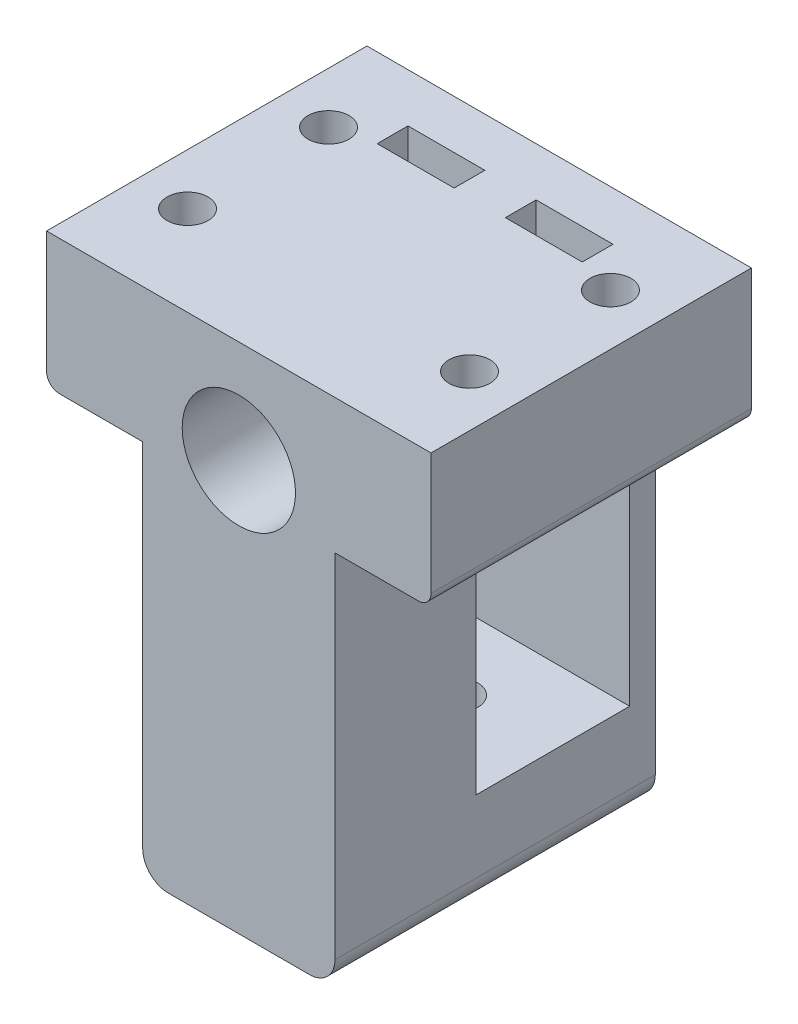
SolidWorks part; units mm, degrees
material "Polyetheretherketone (PEEK)"
ref_plane "Front Plane" through (0, 0, 0) normal (0, 0, 1) x (1, 0, 0)
ref_plane "Top Plane" through (0, 0, 0) normal (0, 1, 0) x (1, 0, 0)
ref_plane "Right Plane" through (0, 0, 0) normal (1, 0, 0) x (0, 0, -1)
sketch "Sketch1" plane through (0, 0, 0) normal (0, 0, 1) x (1, 0, 0)
  line L0 (0, 40) -> (0, 50.5)
  line L3 (0, 50.5) -> (30, 50.5)
  line L7 (0, 40) -> (7.5, 40)
  line L8 (7.5, 10.5) -> (7.5, 40)
  line L11 (30, 40) -> (22.5, 40)
  line L12 (22.5, 10.5) -> (22.5, 40)
  line L13 (30, 40) -> (30, 50.5)
  line L14 (7.5, 10.5) -> (22.5, 10.5)
extrude "Boss-Extrude1" add sketch "Sketch1" along normal blind 25
sketch "Sketch2" plane through (7.5, 0, 0) normal (-1, 0, 0) x (0, 0, 1)
  line L1 (2, 18.13) -> (14, 18.13)
  line L2 (2, 18.13) -> (2, 34.13)
  line L3 (2, 34.13) -> (14, 34.13)
  line L4 (14, 18.13) -> (14, 34.13)
extrude "Cut-Extrude1" cut sketch "Sketch2" against normal through all
sketch "Sketch3" plane through (0, 50.5, 0) normal (0, 1, 0) x (1, 0, 0)
  circle A0 centre (4, -7) radius 1.6
  circle A1 centre (26, -7) radius 1.6
  circle A2 centre (26, -18) radius 1.6
  circle A3 centre (4, -18) radius 1.6
extrude "Cut-Extrude2" cut sketch "Sketch3" against normal through all
sketch "Sketch4" plane through (0, 10.5, 0) normal (0, -1, 0) x (1, 0, 0)
  circle A0 centre (15, 8) radius 1.65
extrude "Cut-Extrude3" cut sketch "Sketch4" against normal up to surface (7.63 mm away) up to face at (15, 18.13, 8)
ref_plane "Plane1" through (0, 0, 15) normal (0, 0, 1) x (1, 0, 0)
sketch "Sketch6" plane through (0, 0, 15) normal (0, 0, 1) x (1, 0, 0)
  circle A0 centre (15, 42.5) radius 4.4196
extrude "Cut-Extrude4" cut sketch "Sketch6" along normal up to surface (10 mm away) up to face at (15, 35.25, 25)
sketch "Sketch7" plane through (0, 0, 0) normal (0, 0, -1) x (-1, 0, 0)
  circle A0 centre (-10, 42.5) radius 1.6
  circle A1 centre (-20, 42.5) radius 1.6
sketch "Sketch8" plane through (0, 0, 0) normal (0, 0, -1) x (-1, 0, 0)
  line L0 (-18.3, 42.5) -> (-11.7, 42.5) construction
  line L1 (-18.3, 45.05) -> (-11.7, 45.05) construction
  line L2 (-18.3, 39.95) -> (-11.7, 39.95) construction
  arc A1 (-18.3, 45.05) -> (-18.3, 39.95) centre (-18.3, 42.5) ccw construction
  arc A2 (-11.7, 39.95) -> (-11.7, 45.05) centre (-11.7, 42.5) ccw construction
  circle A3 centre (-15, 42.5) radius 2.65
  point P3 (-15, 42.5)
extrude "Cut-Extrude6" cut sketch "Sketch8" against normal blind 3
sketch "Sketch9" plane through (0, 34.13, 0) normal (0, -1, 0) x (1, 0, 0)
  circle A0 centre (15, 8) radius 2.45
ref_axis "Axis1" through (15, 34.13, 8) along (0, -1, 0)
ref_plane "Plane2" through (15, 0, 0) normal (-1, 0, 0) x (0, 0, 1)
sketch "Sketch11" plane through (15, 0, 0) normal (-1, 0, 0) x (0, 0, 1)
  line L0 (10.45, 34.13) -> (8, 34.13)
  line L1 (14, 34.13) -> (2, 34.13) construction
  line L2 (5.55, 34.13) -> (10.45, 34.13) construction
  line L3 (8, 34.13) -> (8, 37.36)
  line L4 (8, 37.36) -> (11.15, 37.36)
  line L5 (11.15, 37.36) -> (11.15, 35.66)
  line L6 (10.45, 34.13) -> (10.45, 35.66)
  line L7 (10.45, 35.66) -> (11.15, 35.66)
revolve "Cut-Revolve1" cut sketch "Sketch11" angle 360 about axis through (15, 34.13, 8) along (0, -1, 0) other way angle 360
sketch "Sketch15" plane through (0, 0, 3) normal (0, 0, -1) x (-1, 0, 0)
  circle A1 centre (-15, 42.5) radius 1
ref_plane "Plane3" through (0, 42.5, 0) normal (0, -1, 0) x (-1, 0, 0)
sketch "Sketch16" plane through (0, 42.5, 0) normal (0, -1, 0) x (-1, 0, 0)
  line L0 (-16, -3) -> (-16, -11.0289)
  line L2 (-16.5719, -12.7908) -> (-18.175, -15)
  line L5 (-18.175, -15) -> (-15, -15)
  line L7 (-15, -15) -> (-15, -3)
  line L8 (-15, -3) -> (-16, -3)
  arc A0 (-16.5719, -12.7908) -> (-16, -11.0289) centre (-19, -11.0289) ccw
  dimension "D1" = 3
sketch "Sketch17" plane through (0, 42.5, 0) normal (0, -1, 0) x (-1, 0, 0)
  circle A0 centre (-15, -8) radius 1
loft "Cut-Loft5" cut profiles "Sketch9", "Sketch17" connector at (17.4494, 34.13, 8.0539) connector at (15.9999, 42.5, 8.0126)
ref_axis "Axis2" through (15, 42.5, 25) along (0, 0, -1)
revolve "Cut-Revolve2" cut sketch "Sketch16" angle 360 about axis through (15, 42.5, 25) along (0, 0, -1) other way angle 360
fillet "Fillet4" radius 1 1 edges at (30, 40, 12.5) type face fillet first side face at (30, 45.25, 12.5) second side face at (24.4, 40, 18)
fillet "Fillet5" radius 1 1 edges at (0, 40, 12.5) type face fillet first side face at (0, 45.25, 12.5) second side face at (4, 40, 19.6)
fillet "Fillet6" radius 2 1 edges at (22.5, 10.5, 12.5) type face fillet first side face at (15, 10.5, 6.35) second side face at (22.5, 26.13, 8)
fillet "Fillet7" radius 2 1 edges at (7.5, 10.5, 12.5) type face fillet first side face at (15, 10.5, 6.35) second side face at (7.5, 26.13, 8)
sketch "Sketch18" plane through (0, 50.5, 0) normal (0, 1, 0) x (1, 0, 0)
  line L8 (7, -3.8) -> (13, -3.8)
  line L9 (7, -3.8) -> (7, -6.2)
  line L10 (7, -6.2) -> (13, -6.2)
  line L11 (13, -3.8) -> (13, -6.2)
  line L12 (7, -3.8) -> (13, -6.2) construction
  line L13 (7, -6.2) -> (13, -3.8) construction
  line L14 (17, -3.8) -> (23, -3.8)
  line L15 (17, -3.8) -> (17, -6.2)
  line L16 (17, -6.2) -> (23, -6.2)
  line L17 (23, -3.8) -> (23, -6.2)
  line L18 (17, -3.8) -> (23, -6.2) construction
  line L19 (17, -6.2) -> (23, -3.8) construction
  point P9 (20, -5)
  point P10 (10, -5)
extrude "Cut-Extrude7" cut sketch "Sketch18" against normal blind 10.8
extrude "Cut-Extrude11" cut sketch "Sketch7" against normal blind 8 contours A0
extrude "Cut-Extrude12" cut sketch "Sketch7<3>" against normal blind 8 contours A1
sketch "Sketch7<3>" plane through (0, 0, 0) normal (0, 0, -1) x (-1, 0, 0) same geometry as "Sketch7"
ref_plane "Plane4" through (13, 39.7, 6.2) normal (1, 0, 0) x (0, 0, -1)
